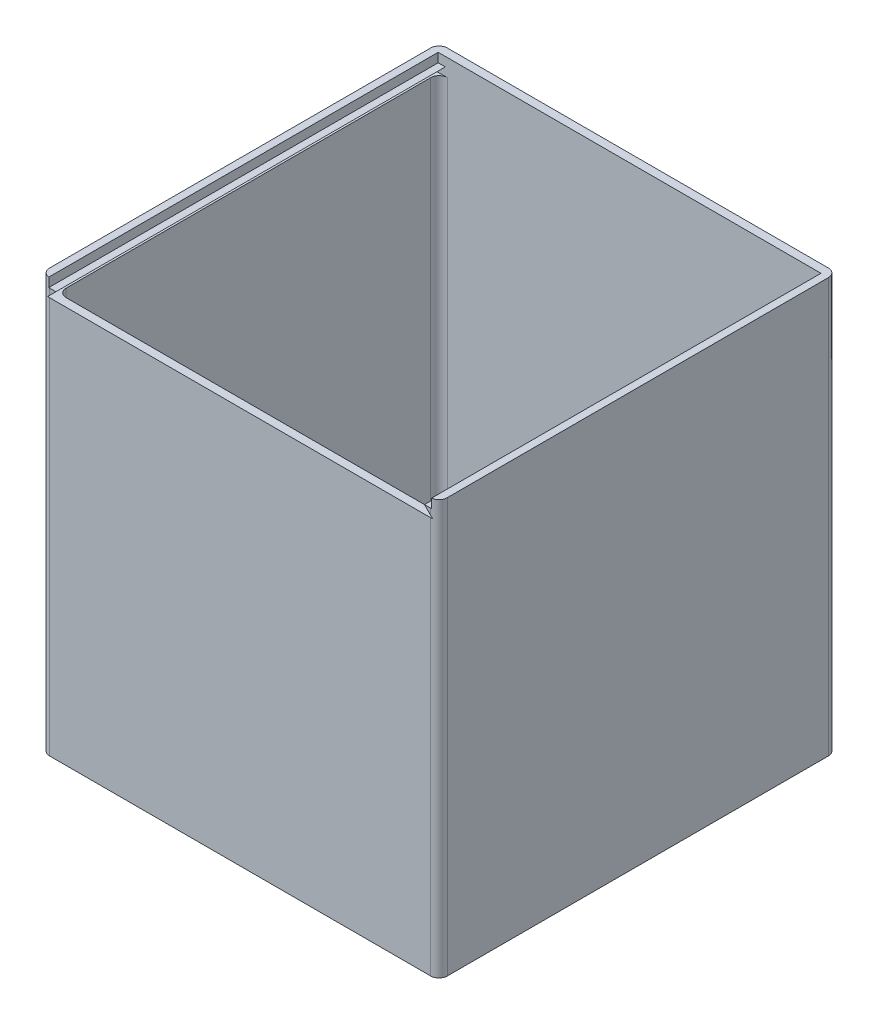
SolidWorks part; units mm, degrees
ref_plane "前视基准面" through (0, 0, 0) normal (0, 0, 1) x (1, 0, 0)
ref_plane "上视基准面" through (0, 0, 0) normal (0, 1, 0) x (1, 0, 0)
ref_plane "右视基准面" through (0, 0, 0) normal (1, 0, 0) x (0, 0, -1)
other "Configuration Table"
sketch "草图1" plane through (0, 0, 0) normal (0, 1, 0) x (1, 0, 0)
  line L1 (-24, 24) -> (24, 24)
  line L2 (-24, 24) -> (-24, -24)
  line L3 (-24, -24) -> (24, -24)
  line L4 (24, 24) -> (24, -24)
  line L5 (-24, 24) -> (24, -24) construction
  line L6 (-24, -24) -> (24, 24) construction
  point P0 (0, 0)
  dimension "D1" = 48
  dimension "D2" = 48
extrude "凸台-拉伸1" add sketch "草图1" along normal blind 50
sketch "草图2" plane through (0, 0, 24) normal (0, 0, 1) x (1, 0, 0)
  line L0 (23, 50) -> (23, 49)
  line L1 (24, 50) -> (24, 0) construction
  line L2 (23, 49) -> (22, 49)
  line L3 (22, 49) -> (23, 48)
  line L4 (23, 48) -> (22, 48)
  line L5 (21, 49) -> (22, 48)
  line L6 (-21, 49) -> (-22, 48)
  line L7 (-23, 48) -> (-22, 48)
  line L8 (-22, 49) -> (-23, 48)
  line L9 (-23, 50) -> (-23, 49)
  line L10 (21, 49) -> (-21, 49)
  line L11 (-22, 49) -> (-23, 49)
  line L12 (-23, 50) -> (23, 50)
  line L13 (-24, 50) -> (24, 50) construction
  line L14 (-24, 50) -> (-24, 0) construction
  line L15 (23.1, 50.1) -> (23.1, 48.9)
  line L16 (23.1, 48.9) -> (22.2414, 48.9)
  line L17 (22.2414, 48.9) -> (23.2414, 47.9)
  line L18 (23.2414, 47.9) -> (21.9586, 47.9)
  line L19 (20.9586, 48.9) -> (21.9586, 47.9)
  line L20 (20.9586, 48.9) -> (-20.9586, 48.9)
  line L21 (-20.9586, 48.9) -> (-21.9586, 47.9)
  line L22 (-23.2414, 47.9) -> (-21.9586, 47.9)
  line L23 (-22.2414, 48.9) -> (-23.2414, 47.9)
  line L24 (-22.2414, 48.9) -> (-23.1, 48.9)
  line L25 (-23.1, 50.1) -> (-23.1, 48.9)
  line L26 (-23.1, 50.1) -> (23.1, 50.1)
  line L27 (-21.9586, 47.9) -> (21.9586, 47.9)
  point P5 (0, 45.7595)
  point P15 (0, 45.7595)
  line M15 (24, 50) -> (-24, 50)
  dimension "D1" = 1
  dimension "D2" = 1
  dimension "D3" = 1
  dimension "D4" = 1
  dimension "D5" = 1
  dimension "D6" = 1
  dimension "D7" = 1
  dimension "D8" = 1
  dimension "D9" = 1
  dimension "D10" = 45
  dimension "D11" = 45
  dimension "D12" = 1
  dimension "D13" = 0.1
extrude "切除-拉伸1" cut sketch "草图2" against normal offset from surface (47 mm away) 1 contours L25 L24 L23 L22 L21 L20 L19 L18 L17 L16 L15 L0 L2 L3 L4 L5 L10 L6 L7 L8 L11 L9 M15 | L11 L8 L7 L6 L10 L5 L4 L3 L2 L0 L9 M15 | L21 L27 L19 L20 region at (23.05, 49.5347, 24) region at (0, 49.4583, 24) region at (0, 48.3961, 24) up to face at (0, 25, -24)
sketch "草图6" plane through (0, 0, 0) normal (0, -1, 0) x (1, 0, 0)
  line L0 (0, -18.168) -> (0, 20.1812) construction
  line L1 (4.2253, 0.4577) -> (2.4855, 16.5192)
  line L2 (-4.2253, 0.4577) -> (-2.4855, 16.5192)
  arc A1 (-4.2253, 0.4577) -> (4.2253, 0.4577) centre (0, 0) ccw
  arc A2 (2.4855, 16.5192) -> (-2.4855, 16.5192) centre (0, 16.25) ccw
  dimension "D1" = 8.5
  dimension "D3" = 5
  dimension "D2" = 23
extrude "切除-拉伸3" cut sketch "草图6" against normal blind 6
shell "抽壳1" thickness 1 removed face at (0, 47.9, 0.5)
sketch "草图3" plane through (0, 0, -23) normal (0, 0, 1) x (1, 0, 0)
  line L0 (-23.2414, 47.9) -> (23.2414, 47.9) construction
  line L1 (0, 57.8815) -> (0, -28.9504) construction
  line L2 (-1.5, 50) -> (-1.5, 47.7581)
  line L3 (-23.1, 50) -> (23.1, 50) construction
  line L4 (1.5, 50) -> (1.5, 47.7581)
  circle A0 centre (0, 39.9) radius 8
  line M7 (23.1, 50) -> (-23.1, 50)
  dimension "D1" = 16
  dimension "D2" = 3
extrude "切除-拉伸2" [suppressed] cut sketch "草图3" against normal up to next contours L1 A0 | A0 L1 | L1 L2 A0 M7 | L1 A0 L4 M7
sketch "草图4" plane through (0, 0, -23) normal (0, 0, 1) x (1, 0, 0)
  line L0 (0, 55.2879) -> (0, -21.7347) construction
  line L1 (-23.2414, 47.9) -> (23.2414, 47.9) construction
  circle A0 centre (-14.75, 44.5) radius 1.4
  circle A1 centre (14.75, 44.5) radius 1.4
  circle A2 centre (-14.75, 44.5) radius 2.9
  circle A3 centre (14.75, 44.5) radius 2.9
  dimension "D1" = 2.8
  dimension "D2" = 2
  dimension "D4" = 1.5
  dimension "D3" = 29.5
extrude "凸台-拉伸2" [suppressed] add sketch "草图4" along normal blind 13
fillet "圆角1" [suppressed] radius 2
sketch "草图7" plane through (0, 6, 0) normal (0, -1, 0) x (1, 0, 0)
  line L0 (4.2253, 0.4577) -> (4.2253, 5.75)
  line L1 (4.2253, 5.75) -> (-4.2253, 5.75)
  line L2 (3.652, 5.75) -> (2.4855, 16.5192)
  line L3 (-2.4855, 16.5192) -> (-3.652, 5.75)
  line L4 (-4.2253, 5.75) -> (-4.2253, 0.4577)
  line L5 (0, -15.6623) -> (0, 21.4263) construction
  arc A0 (-4.2253, 0.4577) -> (4.2253, 0.4577) centre (0, 0) ccw
  circle A1 centre (0, 8.69) radius 0.75
  circle A2 centre (0, 16.24) radius 0.75
  arc A3 (-4.2253, 0.4577) -> (4.2253, 0.4577) centre (0, 0) ccw
  arc A4 (2.4855, 16.5192) -> (-2.4855, 16.5192) centre (0, 16.25) ccw
  arc M1 (-4.2253, 0.4577) -> (4.2253, 0.4577) centre (0, 0) ccw
  line M2 (4.2253, 0.4577) -> (2.4855, 16.5192)
  line M4 (-2.4855, 16.5192) -> (-4.2253, 0.4577)
  dimension "D2" = 1.5
  dimension "D3" = 1.5
  dimension "D1" = 10
  dimension "D4" = 7.55
  dimension "D5" = 8.69
extrude "切除-拉伸4" cut sketch "草图7" against normal up to next contours L5 A3 L1 M2 | L5 L1 M1 M4 | L5 A1 | A1 L5 | L5 A2 | A2 L5 region at (1.9157, 6, 1.0336) region at (-1.9157, 6, 1.0336) region at (-0.3183, 6, 8.69) region at (0.3183, 6, 8.69) region at (0.3183, 6, 16.24) region at (-0.3183, 6, 16.24)
sketch "草图8" plane through (0, 0, 0) normal (0, -1, 0) x (1, 0, 0)
  line L0 (0, 0) -> (9.25, 16.0215)
  line L1 (0, 0) -> (13.0815, -13.0815)
  line L2 (0, 25.6992) -> (0, -26.4148)
  circle A0 centre (0, 0) radius 12.5
  circle A1 centre (0, 0) radius 18.5
  dimension "D1" = 25
  dimension "D2" = 6
  dimension "D3" = 30
  dimension "D4" = 45
extrude "切除-拉伸5" [suppressed] cut sketch "草图8" against normal up to next contours L1 A1 L0 A0
fillet "圆角2" radius 1 16 edges at (0, 1, 19.75) (4.3496, 1, 8.5962) (0, 1, -5.25) (24, 25, -24) (24, 25, 24) (-24, 25, 24) (-24, 25, -24) (-4.3496, 1, 8.5962) (0, 1, -23) (-23, 24.45, -23) (23, 24.45, -23) (23, 1, 0) (23, 24.45, 23) (-23, 1, 0) (0, 1, 23) (-23, 24.45, 23)
sketch "草图9" plane through (0, 1, 0) normal (0, 1, 0) x (1, 0, 0)
  line L1 (-14.1382, 14.3452) -> (-3.751, 14.3452)
  line L2 (-16.1382, 12.3452) -> (-16.1382, 8.7846)
  line L3 (-14.1382, 6.7846) -> (-3.751, 6.7846)
  line L4 (-1.751, 12.3452) -> (-1.751, 8.7846)
  arc A0 (-1.751, 8.7846) -> (-3.751, 6.7846) centre (-3.751, 8.7846) cw
  arc A1 (-1.751, 12.3452) -> (-3.751, 14.3452) centre (-3.751, 12.3452) ccw
  arc A2 (-16.1382, 8.7846) -> (-14.1382, 6.7846) centre (-14.1382, 8.7846) ccw
  arc A3 (-16.1382, 12.3452) -> (-14.1382, 14.3452) centre (-14.1382, 12.3452) cw
  dimension "D1" = 2
extrude "切除-拉伸6" [suppressed] cut sketch "草图9" against normal up to next
sketch "草图10" plane through (0, 6, 0) normal (0, -1, 0) x (1, 0, 0)
  line L3 (-3.652, 5.75) -> (3.652, 5.75)
  line L4 (3.652, 5.75) -> (2.4855, 16.5192)
  line L5 (-2.4855, 16.5192) -> (-3.652, 5.75)
  line L6 (-3.652, 5.75) -> (3.652, 5.75)
  line L7 (3.652, 5.75) -> (2.4855, 16.5192)
  line L8 (-2.4855, 16.5192) -> (-3.652, 5.75)
  circle A0 centre (0, 8.69) radius 0.75 construction
  arc A1 (2.4855, 16.5192) -> (-2.4855, 16.5192) centre (0, 16.25) ccw
  arc A2 (2.4855, 16.5192) -> (-2.4855, 16.5192) centre (0, 16.25) ccw
  circle A3 centre (0, 16.24) radius 0.75 construction
  circle A4 centre (0, 8.69) radius 0.75
  circle A5 centre (0, 16.24) radius 0.75
  dimension "D1" = 0
extrude "凸台-拉伸3" add sketch "草图10" along normal blind 1
